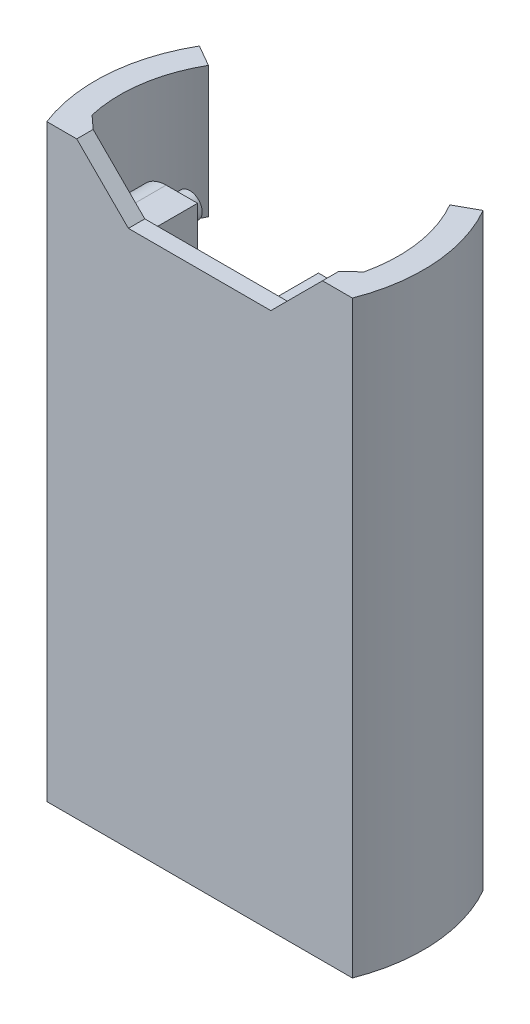
SolidWorks part; units mm, degrees
note: The reader was unsure of these and kept them because the rebuilt part matched: shared geometry of "Sketch1<3>", "Sketch1<4>".
ref_plane "Front Plane" through (0, 0, 0) normal (0, 0, 1) x (1, 0, 0)
ref_plane "Top Plane" through (0, 0, 0) normal (0, 1, 0) x (1, 0, 0)
ref_plane "Right Plane" through (0, 0, 0) normal (1, 0, 0) x (0, 0, -1)
sketch "Sketch1" plane through (0, 0, 0) normal (0, 0, 1) x (-1, 0, 0)
  line L0 (11.8938, -28.5099) -> (11.8938, 28.4901)
  line L1 (11.8938, 28.4901) -> (-11.8938, 28.4901)
  line L2 (-11.8938, 28.4901) -> (-11.8938, -28.5099)
  line L9 (-11.8938, -28.5099) -> (-6.8938, -23.5099)
  line L10 (-6.8938, -23.5099) -> (6.8938, -23.5099)
  line L11 (6.8938, -23.5099) -> (11.8938, -28.5099)
  line L12 (-8.89, -23.3099) -> (-5.85, -23.3099)
  line L13 (-5.85, -23.3099) -> (-5.85, -17.7099)
  line L14 (-5.85, -17.7099) -> (-8.89, -17.7099)
  line L15 (8.89, -17.7099) -> (5.85, -17.7099)
  line L39 (5.85, -17.7099) -> (5.85, -23.3099)
  line L40 (5.85, -23.3099) -> (8.89, -23.3099)
  line L41 (7.89, 27.2813) -> (7.89, 25.2101)
  line L42 (7.89, 25.2101) -> (7.89, 23.1389)
  line L43 (-7.89, 23.1389) -> (-7.89, 25.2101)
  line L44 (-7.89, 25.2101) -> (-7.89, 27.2813)
  line L45 (0, 28.4901) -> (0, -28.4901) construction
  line L46 (-5.85, -20.5099) -> (5.85, -20.5099) construction
  arc A0 (-8.89, -17.7099) -> (-8.89, -23.3099) centre (-8.89, -20.5099) ccw
  circle A3 centre (-8.89, -20.5099) radius 1.2
  circle A4 centre (8.89, -20.5099) radius 1.2
  arc A12 (8.89, -23.3099) -> (8.89, -17.7099) centre (8.89, -20.5099) ccw
  arc A13 (7.89, 23.1389) -> (7.89, 27.2813) centre (8.89, 25.2101) ccw
  circle A14 centre (8.89, 25.2101) radius 1
  circle A15 centre (8.89, 25.2101) radius 1
  circle A16 centre (-8.89, 25.2101) radius 1
  arc A17 (-9.89, 25.2101) -> (-7.89, 25.2101) centre (-8.89, 25.2101) ccw
  arc A18 (-7.89, 25.2101) -> (-9.89, 25.2101) centre (-8.89, 25.2101) ccw
  arc A19 (-7.89, 27.2813) -> (-7.89, 23.1389) centre (-8.89, 25.2101) ccw
  point P17 (8.0237, -8.033)
  point P40 (0, -23.5099)
  point P41 (0, 28.4901)
  point P42 (0, 0)
  point P45 (0, -20.5099)
  point P46 (0, 0)
  point P47 (0, 0)
  point P48 (0, 0)
  point P50 (0, 0)
  point P51 (0, 40.967)
  point P52 (0, -28.5099)
  dimension "D1" = 2.4
  dimension "D2" = 2
  dimension "D3" = 2.8
  dimension "D4" = 11.8938
  dimension "D5" = 3.28
  dimension "D6" = 5.85
  dimension "D7" = 6.8938
  dimension "D8" = 8.89
  dimension "D9" = 57
  dimension "D10" = 3
  dimension "D11" = 3.0038
extrude "Boss-Extrude1" add sketch "Sketch1" along normal blind 1.524 contours L2 L9 L10 L11 L0 L1
extrude "Boss-Extrude2" add sketch "Sketch1<3>" against normal blind 4.064 contours L14 A0 L12 L13 A3 | L40 A12 L15 L39 A4 | L41 A14 L42 A13 | L44 A19 L43 A16 | A4 | A3 | A14 | A16
sketch "Sketch1<3>" plane through (0, 0, 0) normal (0, 0, 1) x (-1, 0, 0) same geometry as "Sketch1"
extrude "Boss-Extrude3" add sketch "Sketch1<4>" against normal blind 6.35 contours A14 | A3 | A16 | A4
sketch "Sketch1<4>" plane through (0, 0, 0) normal (0, 0, 1) x (-1, 0, 0) same geometry as "Sketch1"
sketch "Sketch3" plane through (0, 0, 0) normal (0, 0, -1) x (-1, 0, 0)
  line L0 (8.89, 23.3099) -> (5.85, 23.3099) construction
  line L1 (5.85, 23.3099) -> (5.85, 17.7099) construction
  line L2 (5.85, 17.7099) -> (8.89, 17.7099) construction
  line L3 (-8.89, 17.7099) -> (-5.85, 17.7099) construction
  line L4 (-5.85, 17.7099) -> (-5.85, 23.3099) construction
  line L5 (-5.85, 23.3099) -> (-8.89, 23.3099) construction
  line L6 (-11.8938, -28.4901) -> (11.8938, -28.4901)
  line L7 (11.8938, -28.4901) -> (11.8938, 28.5099)
  line L8 (11.8938, 28.5099) -> (6.8938, 23.5099)
  line L9 (6.8938, 23.5099) -> (-6.8938, 23.5099)
  line L10 (-6.8938, 23.5099) -> (-11.8938, 28.5099)
  line L11 (-11.8938, 28.5099) -> (-11.8938, -28.4901)
  line L12 (-11.8938, -28.4901) -> (11.8938, -28.4901)
  line L13 (11.8938, -28.4901) -> (11.8938, 28.5099)
  line L14 (11.8938, 28.5099) -> (6.8938, 23.5099)
  line L15 (6.8938, 23.5099) -> (-6.8938, 23.5099)
  line L16 (-6.8938, 23.5099) -> (-11.8938, 28.5099)
  line L17 (-11.8938, 28.5099) -> (-11.8938, -28.4901)
  line L18 (8.89, 23.3099) -> (5.85, 23.3099)
  line L19 (5.85, 23.3099) -> (5.85, 17.7099)
  line L20 (5.85, 17.7099) -> (8.89, 17.7099)
  line L21 (-8.89, 17.7099) -> (-5.85, 17.7099)
  line L22 (-5.85, 17.7099) -> (-5.85, 23.3099)
  line L23 (-5.85, 23.3099) -> (-8.89, 23.3099)
  line L25 (-4.7625, 17.7099) -> (4.7625, 17.7099)
  line L26 (-4.7625, 17.7099) -> (-4.7625, 14.5349)
  line L27 (-4.7625, 14.5349) -> (4.7625, 14.5349)
  line L28 (4.7625, 17.7099) -> (4.7625, 14.5349)
  arc A0 (8.89, 17.7099) -> (8.89, 23.3099) centre (8.89, 20.5099) ccw construction
  arc A1 (-8.89, 23.3099) -> (-8.89, 17.7099) centre (-8.89, 20.5099) ccw construction
  arc A2 (8.89, 17.7099) -> (8.89, 23.3099) centre (8.89, 20.5099) ccw
  arc A3 (-8.89, 23.3099) -> (-8.89, 17.7099) centre (-8.89, 20.5099) ccw
  point P17 (0, 17.7099)
  dimension "D2" = 3.175
  dimension "D3" = 9.525
  dimension "D1" = 0
extrude "Boss-Extrude4" add sketch "Sketch3" along normal blind 1.524 contours L28 L25 L26 L27
chamfer "Chamfer1" distance 1.524 angle 45 1 edges at (0, 14.5349, -1.524)
sketch "Sketch4" plane through (0, -28.4901, 0) normal (0, -1, 0) x (1, 0, 0)
  line L0 (11.6929, -10.9367) -> (13.7727, -12.0842)
  line L1 (14.7866, 1.5875) -> (-14.7866, 1.5875)
  line L2 (-13.743, -12.1358) -> (-11.6859, -10.9487)
  line L3 (-13.1556, -1.1594) -> (-11.8938, 0)
  line L4 (-11.8938, 0) -> (11.8938, 0)
  line L5 (11.8938, 0) -> (13.1556, -1.1594)
  arc A0 (13.7727, -12.0842) -> (14.7866, 1.5875) centre (0, -4.1894) ccw
  arc A1 (-14.7866, 1.5875) -> (-13.743, -12.1358) centre (0, -4.1894) ccw
  arc A2 (-13.1556, -1.1594) -> (-11.6859, -10.9487) centre (0, -4.1894) ccw
  arc A3 (11.6929, -10.9367) -> (13.1556, -1.1594) centre (0, -4.1894) ccw
  point P14 (0, 0)
  point P16 (0, 0)
  point P17 (0, 0)
  point P18 (0, 0)
  point P19 (-12.376, -1.339)
  line M2 (11.8938, 0) -> (11.8938, 1.524)
  line M3 (11.8938, 1.524) -> (-11.8938, 1.524)
  line M4 (-11.8938, 1.524) -> (-11.8938, 0)
  dimension "D1" = 13.5
  dimension "D2" = 15.875
  dimension "D3" = 29.5732
  dimension "D4" = 23.7876
  dimension "D5" = 1.5875
extrude "Boss-Extrude5" add sketch "Sketch4" against normal up to vertex (52 mm away) contours A3 L0 A0 L1 A1 L2 A2 L3 L5 M4 M3 M2
sketch "Sketch5" plane through (0, 0, 0) normal (0, 0, -1) x (-1, 0, 0)
  line L0 (11.8938, 28.5099) -> (-11.8938, 28.5099) construction
  line L1 (6.8938, 23.5099) -> (11.8938, 28.5099) construction
  line L2 (-6.8938, 23.5099) -> (6.8938, 23.5099) construction
  line L3 (-11.8938, 28.5099) -> (-6.8938, 23.5099) construction
  line L4 (11.8938, 28.5099) -> (-11.8938, 28.5099)
  line L5 (6.8938, 23.5099) -> (11.8938, 28.5099)
  line L6 (-6.8938, 23.5099) -> (6.8938, 23.5099)
  line L7 (-11.8938, 28.5099) -> (-6.8938, 23.5099)
extrude "Cut-Extrude1" cut sketch "Sketch5" against normal through all
sketch "Sketch6" plane through (0, 0, 0) normal (1, 0, 0) x (0, 0, -1)
  line L0 (12.1358, 28.5099) -> (10.9487, 28.5099) construction
  line L1 (3.048, 15.8099) -> (20.5168, 15.8099)
  line L2 (3.048, 15.8099) -> (3.048, 6.1579)
  line L3 (3.048, 6.1579) -> (20.5168, 6.1579)
  line L4 (20.5168, 15.8099) -> (20.5168, 6.1579)
  line L5 (-1.5875, 28.5099) -> (0, 28.5099) construction
  line L6 (1.1594, 28.5099) -> (0, 28.5099) construction
  line L7 (10.9487, 28.5099) -> (1.1594, 28.5099) construction
  line L8 (12.1358, 28.5099) -> (10.9487, 28.5099)
  line L9 (-1.5875, 28.5099) -> (0, 28.5099)
  line L10 (1.1594, 28.5099) -> (0, 28.5099)
  line L11 (10.9487, 28.5099) -> (1.1594, 28.5099)
  line L16 (0, 23.5099) -> (0, 28.5099)
  line L17 (0, 28.5099) -> (-1.5875, 28.5099)
  line L18 (-1.5875, 28.5099) -> (-1.5875, 23.5099)
  line L19 (-1.5875, 23.5099) -> (0, 23.5099)
  line L20 (0, 23.5099) -> (0, 28.5099)
  line L21 (0, 28.5099) -> (-1.5875, 28.5099)
  line L22 (-1.5875, 28.5099) -> (-1.5875, 23.5099)
  line L23 (-1.5875, 23.5099) -> (0, 23.5099)
  point P11 (20.5168, 8.7003)
  dimension "D2" = 12.7
  dimension "D3" = 3.048
  dimension "D4" = 9.652
  dimension "D1" = 0
extrude "Cut-Extrude2" cut sketch "Sketch6" against normal through all contours L4 L1 L2 L3
sketch "Sketch7" plane through (0, 0, 0) normal (0, 1, 0) x (1, 0, 0)
  line L4 (-13.3346, 6.2961) -> (-11.9337, 7.697)
  line L5 (-11.9337, 7.697) -> (-10.8022, 6.5655)
  line L6 (11.8938, 0) -> (-11.8938, 0)
  line L7 (13.1556, 1.1594) -> (11.8938, 0)
  line L8 (13.7727, 12.0842) -> (11.6929, 10.9367)
  line L9 (-14.7866, -1.5875) -> (14.7866, -1.5875)
  line L10 (-11.6859, 10.9487) -> (-13.743, 12.1358)
  line L11 (-11.8938, 0) -> (-13.1556, 1.1594)
  line L12 (11.8938, 0) -> (-11.8938, 0)
  line L13 (13.1556, 1.1594) -> (11.8938, 0)
  line L14 (13.7727, 12.0842) -> (11.6929, 10.9367)
  line L15 (-14.7866, -1.5875) -> (14.7866, -1.5875)
  line L16 (-11.6859, 10.9487) -> (-13.743, 12.1358)
  line L17 (-11.8938, 0) -> (-13.1556, 1.1594)
  line L18 (-10.8022, 6.5655) -> (-13.4963, 3.8714)
  line L19 (0, 4.1894) -> (0, 17.1669) construction
  line L20 (10.8022, 6.5655) -> (13.4963, 3.8714)
  line L21 (11.9337, 7.697) -> (10.8022, 6.5655)
  line L22 (13.3346, 6.2961) -> (11.9337, 7.697)
  arc A3 (-13.4963, 3.8714) -> (-13.1556, 1.1594) centre (0, 4.1894) ccw
  arc A4 (13.1556, 1.1594) -> (11.6929, 10.9367) centre (0, 4.1894) ccw
  arc A5 (14.7866, -1.5875) -> (13.7727, 12.0842) centre (0, 4.1894) ccw
  arc A6 (-13.743, 12.1358) -> (-14.7866, -1.5875) centre (0, 4.1894) ccw
  arc A7 (-11.6859, 10.9487) -> (-13.1556, 1.1594) centre (0, 4.1894) ccw
  arc A8 (13.1556, 1.1594) -> (13.4963, 3.8714) centre (0, 4.1894) ccw
  arc A9 (14.7866, -1.5875) -> (13.7727, 12.0842) centre (0, 4.1894) ccw
  arc A10 (-13.743, 12.1358) -> (-14.7866, -1.5875) centre (0, 4.1894) ccw
  arc A11 (-11.6859, 10.9487) -> (-13.3346, 6.2961) centre (0, 4.1894) ccw
  arc A12 (13.3346, 6.2961) -> (11.6929, 10.9367) centre (0, 4.1894) ccw
  dimension "D2" = 1.6002
  dimension "D3" = 3.81
  dimension "D4" = 1.9812
  dimension "D5" = 45
  dimension "D1" = 0
extrude "Boss-Extrude6" add sketch "Sketch7" against normal blind 10.16
